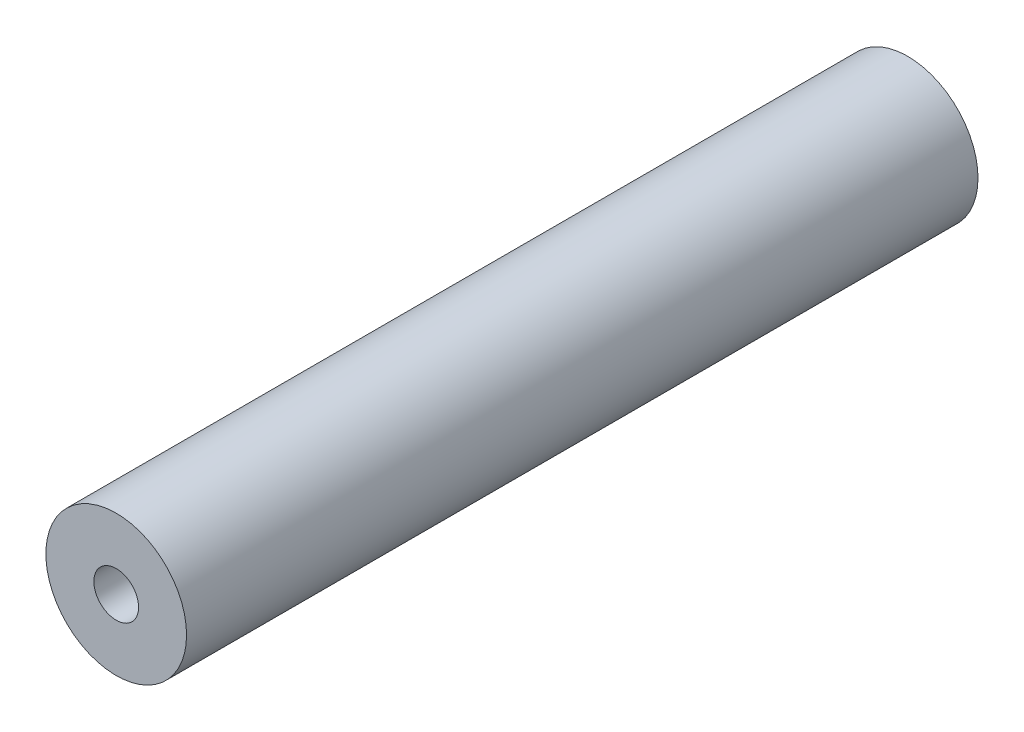
SolidWorks part; units mm, degrees
ref_plane "Front Plane" through (0, 0, 0) normal (0, 0, 1) x (1, 0, 0)
ref_plane "Top Plane" through (0, 0, 0) normal (0, 1, 0) x (1, 0, 0)
ref_plane "Right Plane" through (0, 0, 0) normal (1, 0, 0) x (0, 0, -1)
sketch "Sketch1" plane through (0, 0, 0) normal (0, 0, 1) x (1, 0, 0)
  circle A0 centre (0, 0) radius 6.35
  circle A1 centre (0, 0) radius 2.0193
  dimension "D1" = 4.0386
  dimension "D2" = 12.7
extrude "Boss-Extrude1" add sketch "Sketch1" along normal blind 71.4375
hole_wizard "#10-32 Tapped Hole1" positions "3DSketch1" profile "Sketch2" tap size "#10-32" standard "ANSI Inch" end condition through all
sketch3d "3DSketch1"
  line L0 (0, 0, 71.4375) -> (0, 0, 0) construction
  point P0 (0, 0, 71.4375)
  point P2 (0, 0, 0)
  point P5 (0, 0, 0)
  point P7 (0, 0, 71.4375)
sketch "Sketch2" plane through (0, 0, 71.4375) normal (1, 0, 0) x (0, -1, 0)
  line L0 (0, 0) -> (0, 71.4375)
  line L1 (0, 71.4375) -> (2.0193, 71.4375)
  line L2 (2.0193, 71.4375) -> (2.0193, 0)
  line L5 (2.0193, 0) -> (0, 0)
  line L11 (0, -6.35) -> (0, 107.95) construction
  dimension "Thru Tap Drill Dia." = 4.0386
  dimension "Thru Tap Drill Depth" = 71.4375
cosmetic thread "Hole Thread1" parameters "D2"=4.826
cosmetic thread "Hole Thread2" parameters "D2"=4.826
